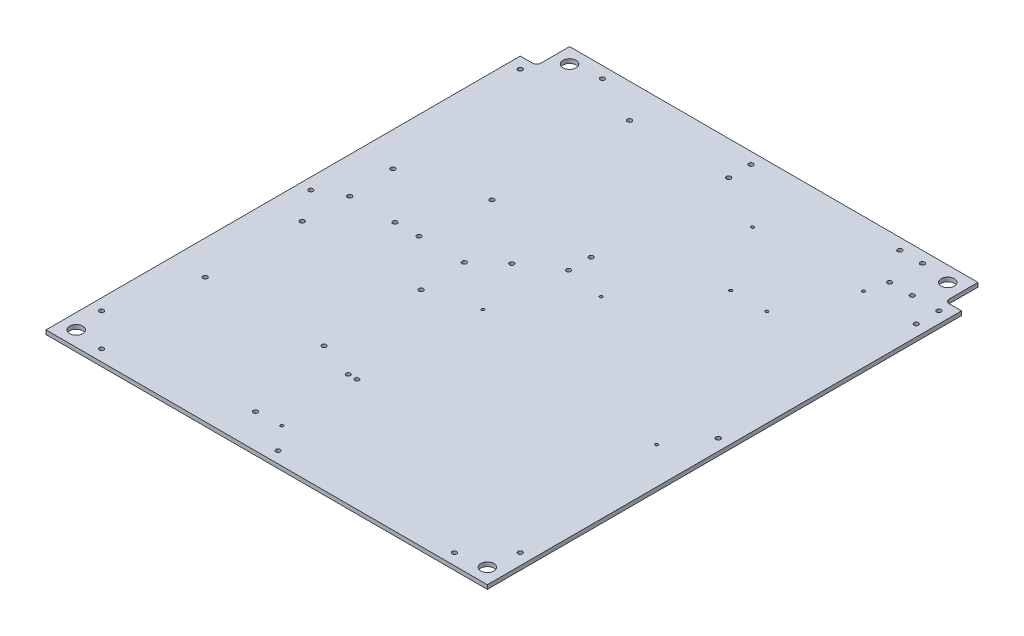
SolidWorks part; units mm, degrees
ref_plane "Front" through (0, 0, 0) normal (0, 0, 1) x (1, 0, 0)
ref_plane "Top" through (0, 0, 0) normal (0, 1, 0) x (1, 0, 0)
ref_plane "Right" through (0, 0, 0) normal (1, 0, 0) x (0, 0, -1)
sketch "Sketch1" plane through (0, 0, 0) normal (0, 1, 0) x (1, 0, 0)
  line L1 (170.434, -195.834) -> (-170.434, -195.834)
  line L2 (170.434, -195.834) -> (170.434, 195.834)
  line L3 (170.434, 195.834) -> (-170.434, 195.834)
  line L4 (-170.434, -195.834) -> (-170.434, 195.834)
  line L5 (170.434, -195.834) -> (-170.434, 195.834) construction
  line L6 (170.434, 195.834) -> (-170.434, -195.834) construction
  point P0 (0, 0)
  dimension "D1" = 340.868
  dimension "D2" = 391.668
extrude "Boss-Extrude1" add sketch "Sketch1" along normal blind 3.175
sketch "Sketch2" plane through (0, 3.175, 0) normal (0, 1, 0) x (1, 0, 0)
  line L0 (170.434, 195.834) -> (-170.434, 195.834) construction
  line L1 (-170.434, 195.834) -> (-157.734, 195.834)
  line L2 (-170.434, 195.834) -> (-170.434, 170.434)
  line L3 (-170.434, 170.434) -> (-160.909, 170.434)
  line L4 (-157.734, 195.834) -> (-157.734, 173.609)
  line L5 (170.434, 195.834) -> (157.734, 195.834)
  line L6 (170.434, 195.834) -> (170.434, 170.434)
  line L7 (170.434, 170.434) -> (160.909, 170.434)
  line L8 (157.734, 195.834) -> (157.734, 173.609)
  arc A0 (-157.734, 173.609) -> (-160.909, 170.434) centre (-160.909, 173.609) cw
  arc A1 (157.734, 173.609) -> (160.909, 170.434) centre (160.909, 173.609) ccw
  dimension "D1" = 3.175
  dimension "D2" = 25.4
  dimension "D3" = 12.7
extrude "Cut-Extrude1" cut sketch "Sketch2" against normal blind 10
hole_wizard "3/8 Clearance Hole1" positions "Sketch3" profile "Sketch4" hole size "3/8" standard "ANSI Inch" end condition through all
sketch "Sketch3" plane through (0, 3.175, 0) normal (0, 1, 0) x (1, 0, 0)
  line L0 (158.75, -184.15) -> (0, -184.15) construction
  line L1 (0, -184.15) -> (-158.75, -184.15) construction
  line L2 (-158.75, -184.15) -> (-158.75, -12.7) construction
  line L3 (-158.75, -12.7) -> (-158.75, 158.75) construction
  line L4 (-158.75, 158.75) -> (158.75, 158.75) construction
  line L5 (158.75, 158.75) -> (158.75, -12.7) construction
  line L6 (158.75, -12.7) -> (158.75, -184.15) construction
  line L8 (146.05, 184.15) -> (0, 184.15) construction
  line L9 (0, 184.15) -> (-146.05, 184.15) construction
  line L10 (-146.05, 184.15) -> (-157.734, 195.834) construction
  line L12 (157.734, 195.834) -> (146.05, 184.15) construction
  line L14 (-158.75, 158.75) -> (-170.434, 170.434) construction
  line L16 (-158.75, -184.15) -> (-170.434, -195.834) construction
  line L18 (158.75, 158.75) -> (170.434, 170.434) construction
  line L20 (158.75, -184.15) -> (170.434, -195.834) construction
  line L21 (158.75, -184.15) -> (158.75, -195.834) construction
  line L22 (-170.434, -195.834) -> (170.434, -195.834) construction
  line L24 (158.75, -184.15) -> (170.434, -184.15) construction
  line L25 (170.434, -195.834) -> (170.434, 170.434) construction
  point P0 (158.75, -184.15)
  point P2 (-158.75, -184.15)
  point P94 (-146.05, 184.15)
  point P96 (146.05, 184.15)
  dimension "D1" = 11.684
sketch "Sketch4" plane through (158.75, 3.175, 184.15) normal (1, 0, 0) x (0, 0, 1)
  line L0 (0, 0) -> (0, 3.175)
  line L1 (0, 3.175) -> (5.0419, 3.175)
  line L2 (5.0419, 3.175) -> (5.0419, 0)
  line L5 (5.0419, 0) -> (0, 0)
  line L11 (0, -6.35) -> (0, 107.95) construction
  dimension "Thru Hole Dia." = 10.0838
  dimension "Thru Hole Depth" = 3.175
hole_wizard "#4-40 Tapped Hole2" positions "Sketch9" profile "Sketch10" tap size "#4-40" standard "ANSI Inch" end condition through all
sketch "Sketch9" plane through (0, 3.175, 0) normal (0, 1, 0) x (1, 0, 0)
  circle A0 centre (33.725, 145.759) radius 1.6319 construction
  circle A1 centre (119.375, 145.759) radius 1.6319 construction
  point P4 (119.375, 145.759)
  point P6 (33.725, 145.759)
  point P20 (21.73, 40.754)
  point P23 (67.7, 94.894)
  point P26 (95.6, 94.894)
  point P30 (-15.34, -13.51)
  point P33 (142.14, -36.73)
  point P36 (142.14, -36.73)
  point P39 (-15.34, -168.81)
cosmetic thread "Hole Thread17" parameters "D2"=2.8448
cosmetic thread "Hole Thread18" parameters "D2"=2.8448
sketch "Sketch10" plane through (119.375, 3.175, -145.759) normal (1, 0, 0) x (0, 0, 1)
  line L0 (0, 0) -> (0, 3.175)
  line L1 (0, 3.175) -> (1.1303, 3.175)
  line L2 (1.1303, 3.175) -> (1.1303, 0)
  line L5 (1.1303, 0) -> (0, 0)
  line L11 (0, -6.35) -> (0, 107.95) construction
  dimension "Thru Tap Drill Dia." = 2.2606
  dimension "Thru Tap Drill Depth" = 3.175
cosmetic thread "Hole Thread19" parameters "D2"=2.8448
cosmetic thread "Hole Thread20" parameters "D2"=2.8448
cosmetic thread "Hole Thread21" parameters "D2"=2.8448
cosmetic thread "Hole Thread22" parameters "D2"=2.8448
cosmetic thread "Hole Thread23" parameters "D2"=2.8448
cosmetic thread "Hole Thread24" parameters "D2"=2.8448
cosmetic thread "Hole Thread25" parameters "D2"=2.8448
hole_wizard "#8-32 Tapped Hole2" positions "Sketch13" profile "Sketch14" tap size "#8-32" standard "ANSI Inch" end condition through all
sketch "Sketch13" plane through (0, 3.175, 0) normal (0, 1, 0) x (1, 0, 0)
  line L34 (-161.684, 161.684) -> (-161.684, -161.684)
  line L36 (161.684, 144.184) -> (161.684, -161.684)
  line L38 (-123.584, 187.084) -> (106.084, 187.084)
  line L39 (106.084, 187.084) -> (123.584, 187.084)
  line L40 (123.584, 187.084) -> (123.584, 161.684)
  line L42 (123.584, 161.684) -> (141.084, 161.684)
  line L43 (141.084, 161.684) -> (161.684, 161.684)
  line L45 (161.684, 161.684) -> (161.684, 144.184)
  line L47 (-8.584, 187.084) -> (-8.584, 169.584)
  line L48 (-8.584, 169.584) -> (-8.584, 63.334)
  line L50 (-8.584, 63.334) -> (-8.584, 45.834)
  line L51 (-8.584, 45.834) -> (-144.184, 45.834)
  line L52 (-144.184, 45.834) -> (-161.684, 45.834)
  line L54 (-34.884, 45.834) -> (-34.884, 28.334)
  line L55 (-34.884, 28.334) -> (-34.884, -169.584)
  line L56 (-34.884, -169.584) -> (-34.884, -187.084)
  line L58 (-136.284, -187.084) -> (136.284, -187.084)
  line L60 (-161.684, -24.166) -> (-144.184, -24.166)
  line L61 (-144.184, -24.166) -> (-52.384, -24.166)
  line L62 (-52.384, -24.166) -> (-34.884, -24.166)
  line L64 (-161.684, -99.166) -> (-144.184, -99.166)
  line L65 (-144.184, -99.166) -> (-52.384, -99.166)
  line L66 (-52.384, -99.166) -> (-34.884, -99.166)
  line L68 (-161.684, 10.834) -> (-142.534, 10.834)
  line L69 (-142.534, 10.834) -> (-107.534, 10.834)
  line L70 (-107.534, 10.834) -> (-89.034, 10.834)
  line L71 (-89.034, 10.834) -> (-54.034, 10.834)
  line L72 (-54.034, 10.834) -> (-34.884, 10.834)
  line L74 (-85.134, 45.834) -> (-85.134, 63.334)
  line L75 (-85.134, 63.334) -> (-85.134, 169.584)
  line L76 (-85.134, 169.584) -> (-85.134, 187.084)
  line L78 (-170.434, 170.434) -> (-170.434, -195.834) construction
  line L79 (157.734, 195.834) -> (-157.734, 195.834) construction
  line L81 (170.434, -195.834) -> (170.434, 170.434) construction
  line L82 (-170.434, -195.834) -> (170.434, -195.834) construction
  line L83 (-170.434, 170.434) -> (-160.909, 170.434) construction
  line L84 (160.909, 170.434) -> (170.434, 170.434) construction
  line L85 (157.734, 195.834) -> (157.734, 173.609) construction
  line L86 (-157.734, 173.609) -> (-157.734, 195.834) construction
  line L87 (-76.384, 45.834) -> (-76.384, 10.834) construction
  line L88 (-76.384, 10.834) -> (-76.384, -24.166) construction
  line L90 (-161.684, 63.334) -> (-85.134, 63.334) construction
  line L92 (-85.134, 63.334) -> (-8.584, 63.334) construction
  point P146 (-161.684, -161.684)
  point P148 (-161.684, 0)
  point P150 (-161.684, 161.684)
  point P152 (-144.184, 45.834)
  point P154 (-8.584, 45.834)
  point P156 (-144.184, -24.166)
  point P158 (-52.384, -24.166)
  point P160 (-144.184, -99.166)
  point P162 (-52.384, -99.166)
  point P164 (-34.884, 28.334)
  point P166 (-34.884, -169.584)
  point P168 (-136.284, -187.084)
  point P170 (0, -187.084)
  point P172 (136.284, -187.084)
  point P174 (161.684, -161.684)
  point P176 (161.684, -8.75)
  point P178 (161.684, 144.184)
  point P180 (141.084, 161.684)
  point P182 (161.684, 161.684)
  point P184 (123.584, 161.684)
  point P186 (123.584, 187.084)
  point P188 (106.084, 187.084)
  point P190 (-123.584, 187.084)
  point P192 (-8.75, 187.084)
  point P194 (-8.584, 169.584)
  point P196 (-8.584, 63.334)
  point P198 (-142.534, 10.834)
  point P200 (-107.534, 10.834)
  point P202 (-89.034, 10.834)
  point P204 (-54.034, 10.834)
  point P206 (-85.134, 63.334)
  point P208 (-85.134, 169.584)
  dimension "D1" = 8.75
  dimension "D2" = 8.75
  dimension "D3" = 8.75
  dimension "D4" = 8.75
  dimension "D5" = 34.15
  dimension "D6" = 8.75
  dimension "D7" = 8.75
  dimension "D8" = 17.5
  dimension "D9" = 34.15
  dimension "D10" = 17.5
  dimension "D11" = 17.5
  dimension "D12" = 34.15
  dimension "D13" = 34.15
  dimension "D14" = 34.15
  dimension "D15" = 34.15
  dimension "D16" = 17.5
  dimension "D17" = 17.5
  dimension "D18" = 17.5
  dimension "D19" = 17.5
  dimension "D20" = 17.5
  dimension "D21" = 17.5
  dimension "D22" = 17.5
  dimension "D23" = 17.5
  dimension "D24" = 150
  dimension "D25" = 161.85
  dimension "D26" = 135.55
  dimension "D27" = 70
  dimension "D28" = 75
  dimension "D29" = 35
  dimension "D30" = 35
  dimension "D31" = 53.5
sketch "Sketch14" plane through (-161.684, 3.175, 161.684) normal (1, 0, 0) x (0, 0, 1)
  line L0 (0, 0) -> (0, 3.175)
  line L1 (0, 3.175) -> (1.7272, 3.175)
  line L2 (1.7272, 3.175) -> (1.7272, 0)
  line L5 (1.7272, 0) -> (0, 0)
  line L11 (0, -6.35) -> (0, 107.95) construction
  dimension "Thread Major Dia." = 3.4544
  dimension "Thru Tap Drill Depth" = 3.175
hole_wizard "#4 Clearance Hole1" positions "Sketch15" profile "Sketch16" hole size "#4" standard "ANSI Inch"
sketch "Sketch15" plane through (0, 3.175, 0) normal (0, 1, 0) x (1, 0, 0)
  point P0 (-23.9256, -108.8644)
  point P3 (-17.2744, -108.8644)
sketch "Sketch16" plane through (-23.9256, 3.175, 108.8644) normal (1, 0, 0) x (0, 0, 1)
  line L0 (0, 0) -> (0, 8.9906)
  line L1 (0, 8.9906) -> (1.6319, 8.01)
  line L2 (1.6319, 8.01) -> (1.6319, 0)
  line L5 (1.6319, 0) -> (0, 0)
  line L10 (0, 8.9906) -> (-1.632, 8.01) construction
  line L11 (0, -6.35) -> (0, 107.95) construction
  dimension "Hole Dia." = 3.2639
  dimension "Hole Depth" = 8.01
  dimension "Drill Angle" = 118
